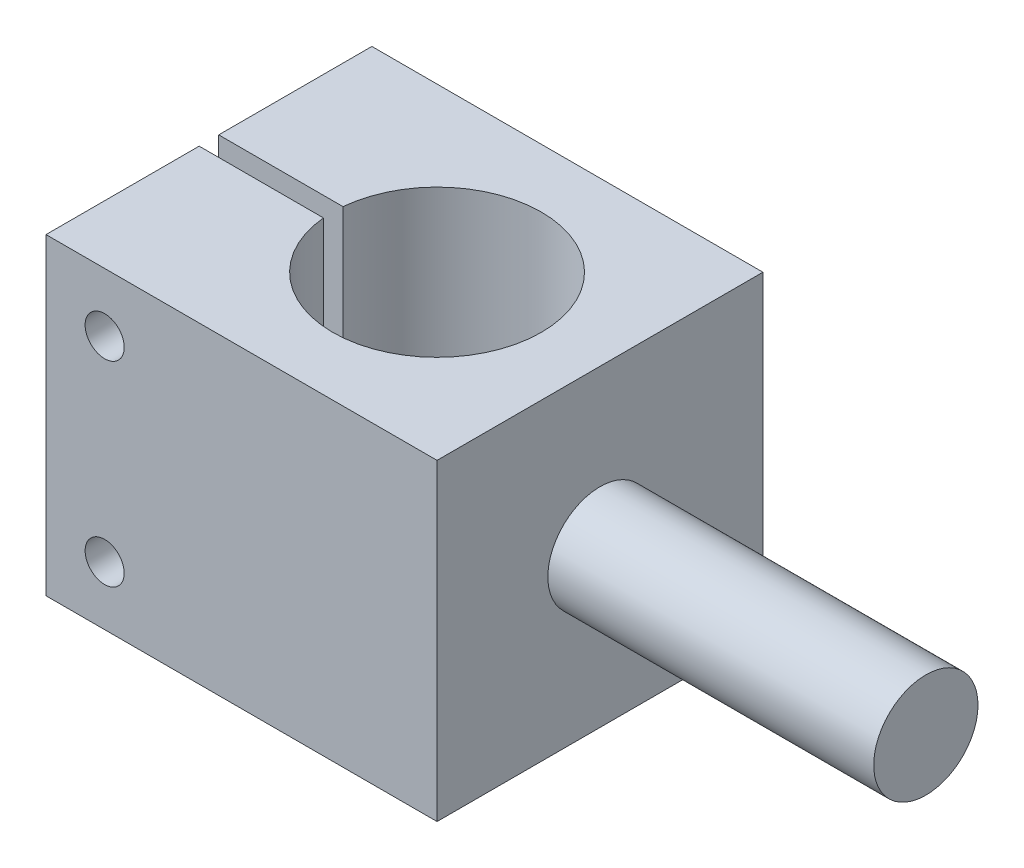
SolidWorks part; units mm, degrees
ref_plane "Front Plane" through (0, 0, 0) normal (0, 0, 1) x (1, 0, 0)
ref_plane "Top Plane" through (0, 0, 0) normal (0, 1, 0) x (1, 0, 0)
ref_plane "Right Plane" through (0, 0, 0) normal (1, 0, 0) x (0, 0, -1)
sketch "Sketch1" plane through (0, 0, 0) normal (0, 1, 0) x (1, 0, 0)
  line L0 (0, 36.6081) -> (0, -34.2652) construction
  line L1 (-53.4185, 0) -> (59.9787, 0) construction
  line L2 (-30, 0) -> (-30, 25)
  line L3 (-30, 25) -> (0, 25)
  line L4 (-30, 0) -> (0, 0)
  line L5 (0, 25) -> (0, 0)
  dimension "D1" = 25
  dimension "D2" = 30
extrude "Boss-Extrude1" add sketch "Sketch1" along normal blind 24
sketch "Sketch2" plane through (0, 0, 0) normal (0, -1, 0) x (1, 0, 0)
  line L0 (-30, 0) -> (0, 0) construction
  line L1 (0, 0) -> (0, -25) construction
  line L2 (-42.4526, -12.5) -> (15.996, -12.5) construction
  line L3 (-20.4648, -11.75) -> (-30, -11.75)
  line L4 (-30, -25) -> (-30, 0) construction
  line L5 (-30, -11.75) -> (-30, -12.5)
  line L6 (-20.4648, -13.25) -> (-30, -13.25)
  line L7 (-30, -13.25) -> (-30, -12.5)
  circle A0 centre (-12.5, -12.5) radius 8
  arc A1 (-20.4648, -11.75) -> (-20.4648, -13.25) centre (-12.5, -12.5) cw
  line M6 (-30, 0) -> (-30, -25)
  dimension "D1" = 16
  dimension "D2" = 12.5
  dimension "D3" = 12.5
  dimension "D4" = 0.75
  dimension "D5" = 0.75
extrude "Cut-Extrude1" cut sketch "Sketch2" against normal through all contours L2 A0 | A0 L2 A1 | L2 L6 A0 M6 | L2 A0 L3 M6 region at (-25.2441, 0, -12.1248) region at (-25.2441, 0, -12.8752) region at (-12.5, 0, -9.1047) region at (-12.5, 0, -15.8953)
sketch "Sketch3" plane through (0, 0, 0) normal (0, 0, 1) x (1, 0, 0)
  line L0 (-30, 24) -> (-30, 0) construction
  line L1 (-30, 0) -> (0, 0) construction
  line L2 (-30, 24) -> (0, 24) construction
  circle A0 centre (-25.5, 19.5) radius 1.5
  circle A1 centre (-25.5, 4.5) radius 1.5
  dimension "D1" = 3
  dimension "D2" = 4.5
  dimension "D3" = 4.5
  dimension "D4" = 4.5
extrude "Cut-Extrude2" cut sketch "Sketch3" against normal through all
sketch "Sketch4" plane through (0, 0, 0) normal (1, 0, 0) x (0, 0, -1)
  line L2 (0, 24) -> (25, 24) construction
  line L3 (0, 24) -> (0, 0) construction
  circle A0 centre (12.5, 12) radius 4
  dimension "D1" = 8
  dimension "D2" = 12
  dimension "D3" = 12.5
sketch "Sketch5" plane through (0, 0, 0) normal (1, 0, 0) x (0, 0, -1)
  line L0 (-5.5298, 12) -> (30.6973, 12) construction
  line L1 (12.5, 24.9191) -> (12.5, -1.5558) construction
  line L2 (0, 24) -> (0, 0) construction
  line L4 (0, 24) -> (25, 24) construction
  circle A0 centre (12.5, 12) radius 4
  dimension "D3" = 8
  dimension "D1" = 12.5
  dimension "D2" = 12
extrude "Boss-Extrude3" add sketch "Sketch5" along normal blind 18.5
extrude "Boss-Extrude2" add sketch "Sketch4" along normal blind 25
